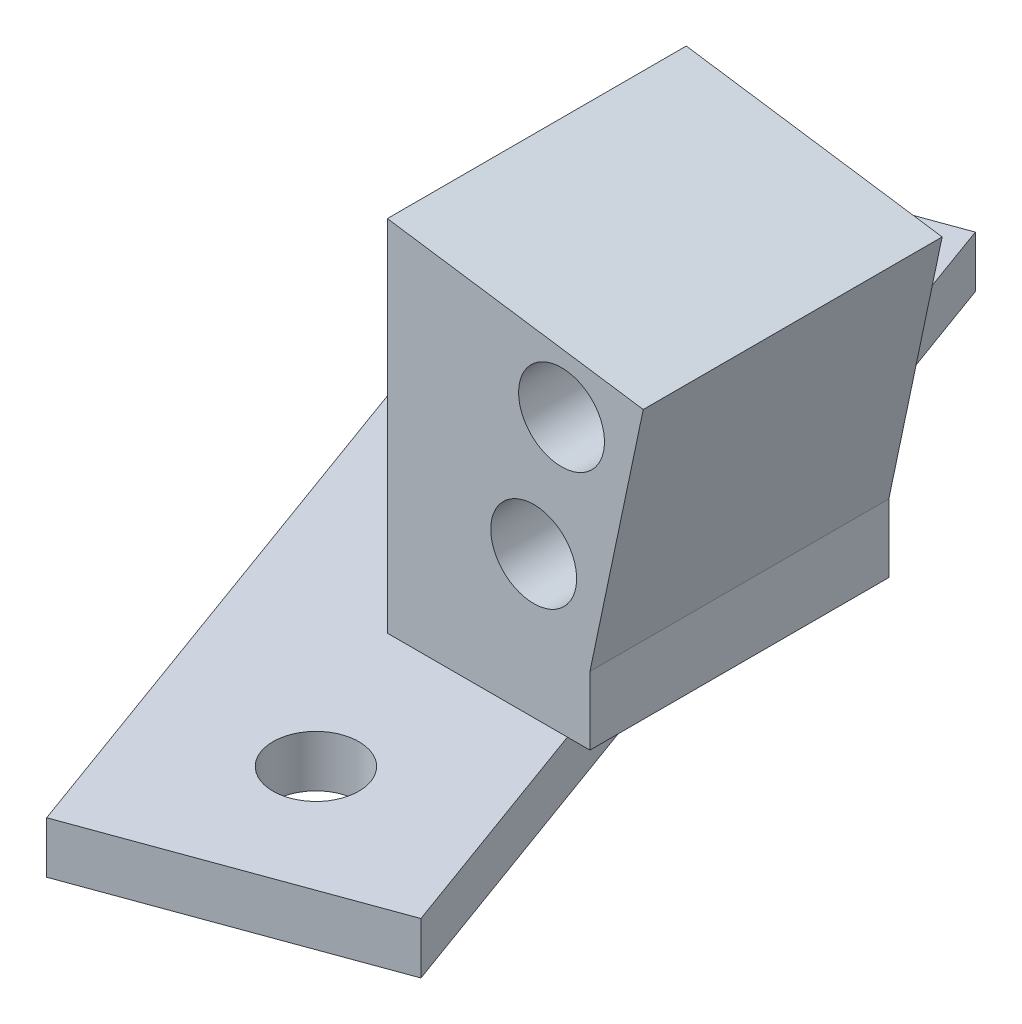
SolidWorks part; units mm, degrees
ref_plane "Front Plane" through (0, 0, 0) normal (0, 0, 1) x (1, 0, 0)
ref_plane "Top Plane" through (0, 0, 0) normal (0, 1, 0) x (1, 0, 0)
ref_plane "Right Plane" through (0, 0, 0) normal (1, 0, 0) x (0, 0, -1)
sketch "Sketch1" plane through (0, 0, 0) normal (0, 0, 1) x (1, 0, 0)
  line L0 (-629.0113, 228.5148) -> (-646.4173, 232.1744)
  line L1 (-625.5069, 227.7779) -> (-640.2031, 230.8679) construction
  line L2 (-646.4173, 232.1744) -> (-650.3578, 213.4325)
  line L3 (-650.3578, 213.4325) -> (-632.9518, 209.7729)
  line L4 (-626.0822, 208.3286) -> (-644.038, 212.1038) construction
  line L5 (-632.9518, 209.7729) -> (-629.0113, 228.5148)
  circle A0 centre (-635.0536, 225) radius 3.175
  circle A1 centre (-637.1112, 215.214) radius 3.175
  dimension "D4" = 6.35
  dimension "D5" = 6.35
  dimension "D1" = 6.35
  dimension "D2" = 19.1516
  dimension "D3" = 17.7865
extrude "Boss-Extrude1" add sketch "Sketch1" along normal up to surface (22.098 mm away)
sketch "Sketch2" plane through (15.4424, 73.4471, 0) normal (-0.2058, -0.9786, 0) x (0.9786, -0.2058, 0)
  line L0 (-680.3571, 22.098) -> (-680.3571, 0)
  line L1 (-680.3571, 0) -> (-673.9925, 0)
  line L2 (-680.3571, 0) -> (-662.5706, 0) construction
  line L3 (-673.9925, 0) -> (-673.9925, 22.098)
  line L4 (-662.5706, 22.098) -> (-680.3571, 22.098) construction
  line L5 (-673.9925, 22.098) -> (-680.3571, 22.098)
  dimension "D1" = 6.3646
extrude "Boss-Extrude2" add sketch "Sketch2" along normal blind 8.89 contours L5 L0 L1 L3
ref_plane "Plane5" through (0, 204.7328, 0) normal (0, 1, 0) x (1, 0, 0)
sketch "Sketch12" plane through (0, 204.7328, 0) normal (0, 1, 0) x (1, 0, 0)
  line L0 (-672.1633, 17.9339) -> (-648.7076, -46.5102)
  line L1 (-648.7076, -46.5102) -> (-628.4196, -39.126)
  line L2 (-628.4196, -39.126) -> (-651.8754, 25.3181)
  line L3 (-651.8754, 25.3181) -> (-672.1633, 17.9339)
  line L5 (-646.4173, -22.098) -> (-629.0113, -22.098) construction
  circle A0 centre (-658.5444, 12.0787) radius 3.175
  circle A1 centre (-642.0385, -33.2709) radius 3.175
  dimension "D5" = 10.16
  dimension "D7" = 6.35
  dimension "D10" = 6.35
  dimension "D2" = 110
  dimension "D3" = 5.08
  dimension "D4" = 24.13
  dimension "D6" = 10.795
  dimension "D8" = 10.795
  dimension "D9" = 10.16
  dimension "D11" = 68.58
  dimension "D12" = 21.59
extrude "Boss-Extrude6" add sketch "Sketch12" against normal blind 3.81
sketch "Sketch19" plane through (0, 0, 22.098) normal (0, 0, 1) x (1, 0, 0)
  line L0 (-646.4173, 232.1744) -> (-654.0373, 232.1744)
  line L1 (-654.0373, 232.1744) -> (-654.0373, 204.7328)
  line L2 (-672.1633, 204.7328) -> (-648.7076, 204.7328) construction
  line L3 (-654.0373, 204.7328) -> (-652.1869, 204.7328)
  line L4 (-652.1869, 204.7328) -> (-646.4173, 232.1744)
  dimension "D1" = 7.62
extrude "Boss-Extrude12" add sketch "Sketch19" against normal up to surface (22.098 mm away) up to face at (-641.73, 215.3418, 0)
sketch "Sketch20" plane through (0, 0, 0) normal (0, 0, -1) x (-1, 0, 0)
  line L0 (629.0113, 228.5148) -> (654.0373, 232.1744)
  line L1 (654.0373, 232.1744) -> (646.4173, 232.1744)
  line L2 (646.4173, 232.1744) -> (629.0113, 228.5148)
extrude "Cut-Extrude1" cut sketch "Sketch20" against normal blind 35.052
sketch "Sketch21" plane through (0, 0, 0) normal (0, 0, -1) x (-1, 0, 0)
  line L0 (644.1294, 212.123) -> (644.1294, 204.7328)
  line L1 (419.4444, 204.7328) -> (-419.4444, 204.7328) construction
  line L2 (644.1294, 204.7328) -> (645.6832, 204.7328)
  line L3 (645.6832, 204.7328) -> (644.1294, 212.123) construction
  line L4 (645.6832, 204.7328) -> (644.1294, 212.123)
extrude "Boss-Extrude13" add sketch "Sketch21" against normal blind 22.098
sketch "Sketch22" plane through (0, 204.7328, 0) normal (0, 1, 0) x (1, 0, 0)
  line L4 (-644.1294, 0) -> (-644.1294, -22.098)
  line L5 (-632.9518, 0) -> (-644.1294, 0)
  line L6 (-632.9518, -22.098) -> (-632.9518, 0)
  line L7 (-644.1294, -22.098) -> (-632.9518, -22.098)
  line L8 (-644.1294, 0) -> (-644.1294, -22.098)
  line L9 (-632.9518, 0) -> (-644.1294, 0)
  line L10 (-632.9518, -22.098) -> (-632.9518, 0)
  line L11 (-644.1294, -22.098) -> (-632.9518, -22.098)
  dimension "D1" = 0
extrude "Boss-Extrude14" add sketch "Sketch22" along normal up to body
sketch "Sketch23" plane through (0, 0, 22.098) normal (0, 0, 1) x (1, 0, 0)
  line L0 (-647.9291, 231.2812) -> (-647.9291, 204.7328)
  line L1 (-629.0113, 228.5148) -> (-654.0373, 232.1744) construction
  line L2 (-654.0373, 204.7328) -> (-634.6173, 204.7328) construction
  line L3 (-647.9291, 204.7328) -> (-654.0373, 204.7328)
  line L4 (-654.0373, 204.7328) -> (-654.0373, 232.1744)
  line L5 (-654.0373, 232.1744) -> (-654.0373, 204.7328) construction
  line L6 (-654.0373, 232.1744) -> (-647.9291, 231.2812)
extrude "Cut-Extrude3" cut sketch "Sketch23" against normal blind 39.878
